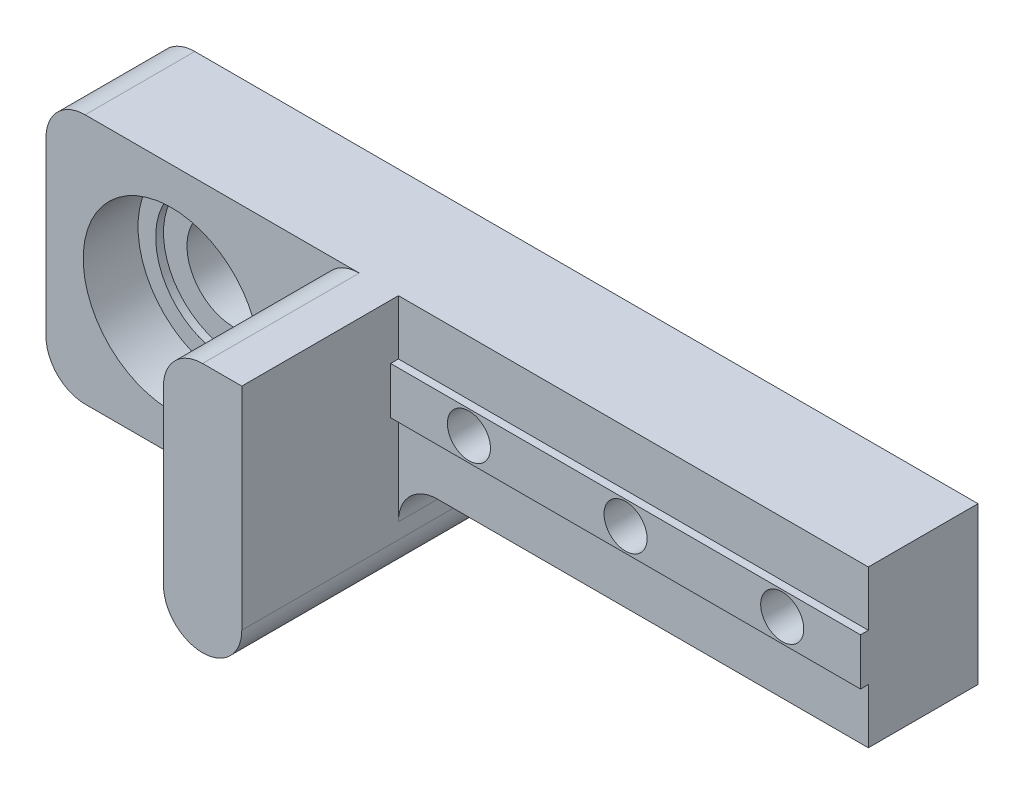
SolidWorks part; units mm, degrees
ref_plane "Alzado" through (0, 0, 0) normal (0, 0, 1) x (1, 0, 0)
ref_plane "Planta" through (0, 0, 0) normal (0, 1, 0) x (1, 0, 0)
ref_plane "Vista lateral" through (0, 0, 0) normal (1, 0, 0) x (0, 0, -1)
sketch "Croquis2" plane through (0, 0, 0) normal (0, 0, 1) x (1, 0, 0)
  line L0 (0, 0) -> (-105, 0)
  line L1 (-105, 0) -> (-105, -32)
  line L2 (-105, -32) -> (-60, -32)
  line L3 (-60, -32) -> (-60, -20)
  line L4 (-60, -20) -> (0, -20)
  line L5 (0, -20) -> (0, 0)
  dimension "D1" = 45
  dimension "D2" = 60
  dimension "D3" = 20
  dimension "D4" = 32
extrude "Saliente-Extruir1" add sketch "Croquis2" along normal blind 14
sketch "Croquis3" plane through (0, 0, 14) normal (0, 0, 1) x (1, 0, 0)
  line L0 (0, 0) -> (-105, 0) construction
  line L1 (-105, 0) -> (-105, -32) construction
  circle A0 centre (-89, -16) radius 11.25
  dimension "D3" = 22.5
  dimension "D1" = 16
  dimension "D2" = 16
extrude "Cortar-Extruir1" cut sketch "Croquis3" against normal blind 7
sketch "Croquis4" plane through (0, 0, 7) normal (0, 0, 1) x (1, 0, 0)
  circle A0 centre (-89, -16) radius 9
  dimension "D1" = 18
extrude "Cortar-Extruir2" cut sketch "Croquis4" against normal blind 1
sketch "Croquis5" plane through (0, 0, 6) normal (0, 0, 1) x (1, 0, 0)
  circle A0 centre (-89, -16) radius 6
  dimension "D1" = 12
extrude "Cortar-Extruir3" cut sketch "Croquis5" against normal up to next
sketch "Croquis6" plane through (0, 0, 0) normal (0, 0, -1) x (-1, 0, 0)
  line L0 (0, 0) -> (105, 0) construction
  line L1 (0, -20) -> (0, 0) construction
  circle A0 centre (10, -10) radius 2.75
  circle A1 centre (30, -10) radius 2.75
  circle A3 centre (50, -10) radius 2.75
  dimension "D1" = 5.5
  dimension "D2" = 5.5
  dimension "D8" = 5.5
  dimension "D3" = 10
  dimension "D4" = 10
  dimension "D5" = 20
  dimension "D6" = 10
  dimension "D7" = 20
  dimension "D9" = 10
sketch "Croquis8" plane through (0, 0, 14) normal (0, 0, 1) x (1, 0, 0)
  line L0 (-60, -32) -> (-60, 0)
  line L1 (0, 0) -> (-105, 0) construction
  line L2 (-60, 0) -> (-70, 0)
  line L3 (-70, 0) -> (-70, -32)
  line L4 (-105, -32) -> (-60, -32) construction
  line L5 (-70, -32) -> (-60, -32)
  dimension "D1" = 10
extrude "Saliente-Extruir4" add sketch "Croquis8" along normal blind 20
fillet "Redondeo1" radius 5 6 edges at (-70, 0, 24) (-70, -32, 24) (-60, -20, 7) (-105, -32, 7) (-105, 0, 7) (-60, -32, 17)
sketch "Croquis10" plane through (0, 0, 14) normal (0, 0, 1) x (1, 0, 0)
  line L0 (0, -7) -> (0, -13)
  line L1 (0, -20) -> (0, 0) construction
  line L2 (0, -13) -> (-60, -13)
  line L3 (-60, -27) -> (-60, 0) construction
  line L4 (-60, -13) -> (-60, -7)
  line L5 (-60, -7) -> (0, -7)
  line L6 (0, 0) -> (-60, 0) construction
  point P4 (0, -10)
  dimension "D1" = 10
  dimension "D2" = 6
extrude "Saliente-Extruir7" add sketch "Croquis10" along normal blind 1 contours L2 L4 L5 L0
extrude "Cortar-Extruir6" cut sketch "Croquis6" against normal blind 40 contours A1 | A0 | A3
sketch "Croquis11" plane through (0, 0, 0) normal (0, 0, -1) x (-1, 0, 0)
  circle A0 centre (10, -10) radius 6
  circle A1 centre (30, -10) radius 6
  circle A2 centre (50, -10) radius 6
  dimension "D1" = 12
  dimension "D2" = 12
  dimension "D3" = 12
extrude "Cortar-Extruir7" cut sketch "Croquis11" against normal blind 8
